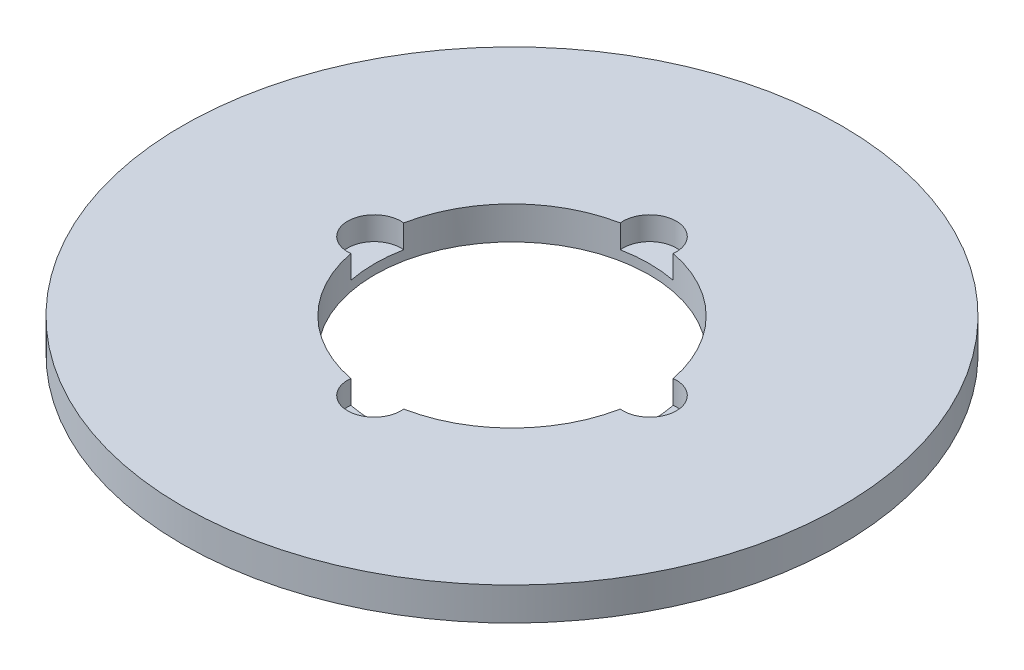
SolidWorks part; units mm, degrees
ref_plane "Front Plane" through (0, 0, 0) normal (0, 0, 1) x (1, 0, 0)
ref_plane "Top Plane" through (0, 0, 0) normal (0, 1, 0) x (1, 0, 0)
ref_plane "Right Plane" through (0, 0, 0) normal (1, 0, 0) x (0, 0, -1)
sketch "Sketch1" plane through (0, 0, 0) normal (0, 1, 0) x (1, 0, 0)
  circle A0 centre (0, 0) radius 90
  dimension "FLANGE_OD" = 180
extrude "Boss-Extrude1" add sketch "Sketch1" along normal blind 9
sketch "Sketch2" plane through (0, 0, 0) normal (0, 1, 0) x (1, 0, 0)
  circle A0 centre (0, 0) radius 37.5
  dimension "BORE_D" = 75
extrude "Cut-Extrude1" cut sketch "Sketch2" along normal through all
sketch "Sketch3" plane through (0, 9, 0) normal (0, 1, 0) x (1, 0, 0)
  circle A0 centre (0, 0) radius 37.6018 construction
  circle A1 centre (-37.6018, 0) radius 7.2711
  dimension "BOLT_D" = 14.5422
  dimension "BOLT_PCD" = 75.2035
extrude "Cut-Extrude2" cut sketch "Sketch3" against normal blind 6.3563
pattern_circular "CirPattern1" count 4 over 360 about axis through (0, 0, 0) along (0, 1, 0) of "Cut-Extrude2"
